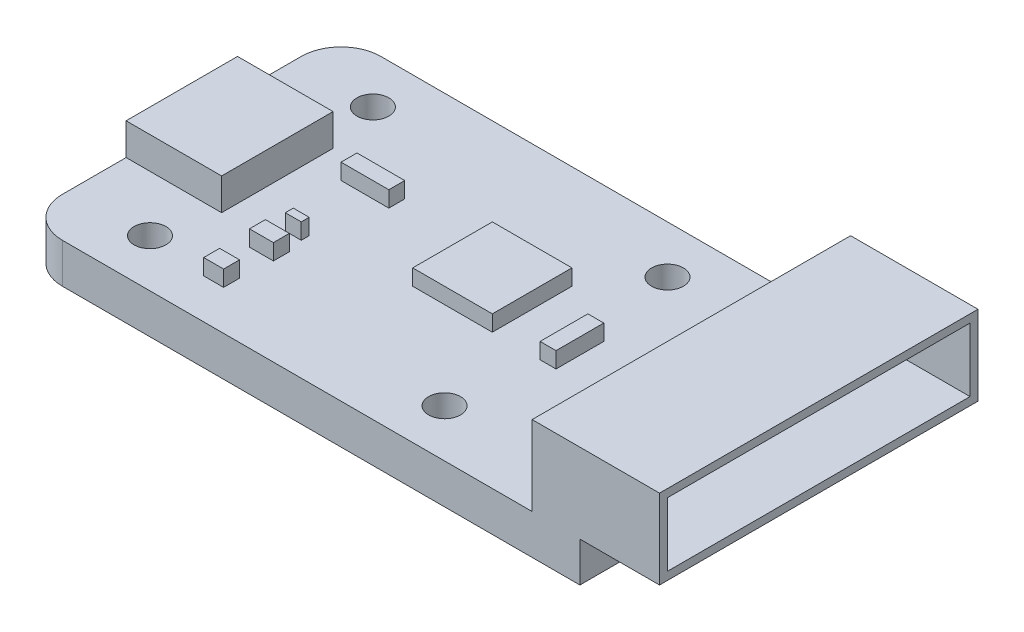
SolidWorks part; units mm, degrees
ref_plane "Front Plane" through (0, 0, 0) normal (0, 0, 1) x (1, 0, 0)
ref_plane "Top Plane" through (0, 0, 0) normal (0, 1, 0) x (1, 0, 0)
ref_plane "Right Plane" through (0, 0, 0) normal (1, 0, 0) x (0, 0, -1)
sketch "Sketch1" plane through (0, 0, 0) normal (0, 1, 0) x (1, 0, 0)
  line L1 (-17.5, -10) -> (17.5, -10)
  line L2 (-17.5, -10) -> (-17.5, 10)
  line L3 (-17.5, 10) -> (17.5, 10)
  line L4 (17.5, -10) -> (17.5, 10)
  line L5 (-17.5, -10) -> (17.5, 10) construction
  line L6 (-17.5, 10) -> (17.5, -10) construction
  point P0 (0, 0)
  dimension "D1" = 35
  dimension "D2" = 20
extrude "Boss-Extrude1" add sketch "Sketch1" along normal blind 2.5
fillet "Fillet1" radius 2.5 2 edges at (-17.5, 1.25, -10) (-17.5, 1.25, 10)
sketch "Sketch2" plane through (0, 2.5, 0) normal (0, 1, 0) x (1, 0, 0)
  line L0 (-17.5, 0) -> (17.5, 0) construction
  line L1 (-17.5, 7.5) -> (-17.5, -7.5) construction
  line L2 (17.5, -10) -> (17.5, 10) construction
  line L3 (17.5, 10) -> (-15, 10) construction
  circle A0 centre (-12.5, 7) radius 1
  circle A1 centre (6, 7) radius 1
  circle A2 centre (6, -7) radius 1
  circle A3 centre (-12.5, -7) radius 1
  point P12 (0, 0)
  dimension "D1" = 2
  dimension "D2" = 3
  dimension "D3" = 5
  dimension "D4" = 18.5
extrude "Cut-Extrude1" cut sketch "Sketch2" against normal up to surface (2.5 mm away) up to face at (-5.1726, 0, 0)
sketch "Sketch3" plane through (0, 2.5, 0) normal (0, 1, 0) x (1, 0, 0)
  line L0 (-17.5, 7.5) -> (-17.5, -7.5) construction
  line L1 (-11.5, -3.5) -> (-17.5, -3.5)
  line L2 (-11.5, -3.5) -> (-11.5, 3.5)
  line L3 (-11.5, 3.5) -> (-17.5, 3.5)
  line L4 (-17.5, -3.5) -> (-17.5, 3.5)
  line L5 (-11.5, -3.5) -> (-17.5, 3.5) construction
  line L6 (-11.5, 3.5) -> (-17.5, -3.5) construction
  point P0 (-14.5, 0)
  point P5 (0, 0)
  dimension "D1" = 7
  dimension "D2" = 6
  dimension "D3" = 3
extrude "Boss-Extrude2" add sketch "Sketch3" along normal blind 2
sketch "Sketch4" plane through (-17.5, 0, 0) normal (-1, 0, 0) x (0, 0, 1)
  line L1 (-3.25, 4.25) -> (3.25, 4.25)
  line L2 (-3.25, 4.25) -> (-3.25, 2.75)
  line L3 (-3.25, 2.75) -> (3.25, 2.75)
  line L4 (3.25, 4.25) -> (3.25, 2.75)
  line L5 (-3.25, 4.25) -> (3.25, 2.75) construction
  line L6 (-3.25, 2.75) -> (3.25, 4.25) construction
  point P0 (0, 3.5)
  point P5 (0, 0)
  point P7 (0, 0)
  dimension "D1" = 6.5
  dimension "D2" = 1.5
  dimension "D3" = 3.5
extrude "Cut-Extrude2" cut sketch "Sketch4" against normal blind 5.5
sketch "Sketch5" plane through (0, 2.5, 0) normal (0, 1, 0) x (1, 0, 0)
  line L0 (17.5, -10) -> (17.5, 10) construction
  line L1 (14.5, -10) -> (22.5, -10)
  line L2 (14.5, -10) -> (14.5, 10)
  line L3 (14.5, 10) -> (22.5, 10)
  line L4 (22.5, -10) -> (22.5, 10)
  line L5 (14.5, -10) -> (22.5, 10) construction
  line L6 (14.5, 10) -> (22.5, -10) construction
  point P0 (18.5, 0)
  point P7 (0, 0)
  dimension "D1" = 8
  dimension "D2" = 5
  dimension "D3" = 20
extrude "Boss-Extrude3" add sketch "Sketch5" along normal blind 5
sketch "Sketch6" plane through (22.5, 0, 0) normal (1, 0, 0) x (0, 0, -1)
  line L1 (-9.5, 3) -> (9.5, 3)
  line L2 (-9.5, 3) -> (-9.5, 7)
  line L3 (-9.5, 7) -> (9.5, 7)
  line L4 (9.5, 3) -> (9.5, 7)
  line L5 (-9.5, 3) -> (9.5, 7) construction
  line L6 (-9.5, 7) -> (9.5, 3) construction
  point P0 (0, 5)
  point P5 (0, 0)
  dimension "D1" = 5
  dimension "D2" = 4
  dimension "D3" = 19
extrude "Cut-Extrude3" cut sketch "Sketch6" against normal blind 7
sketch "Sketch7" plane through (0, 2.5, 0) normal (0, 1, 0) x (1, 0, 0)
  line L0 (-17.5, 7.5) -> (-17.5, 3.5) construction
  line L1 (-1.5, -1.5) -> (3.5, -1.5)
  line L2 (-1.5, -1.5) -> (-1.5, 3.5)
  line L3 (-1.5, 3.5) -> (3.5, 3.5)
  line L4 (3.5, -1.5) -> (3.5, 3.5)
  line L5 (-1.5, -1.5) -> (3.5, 3.5) construction
  line L6 (-1.5, 3.5) -> (3.5, -1.5) construction
  line L7 (14.5, 10) -> (-15, 10) construction
  point P0 (1, 1)
  dimension "D1" = 5
  dimension "D2" = 5
  dimension "D3" = 18.5
  dimension "D4" = 9
extrude "Boss-Extrude4" add sketch "Sketch7" along normal blind 1
sketch "Sketch8" plane through (0, 2.5, 0) normal (0, 1, 0) x (1, 0, 0)
  line L0 (-15, -10) -> (14.5, -10) construction
  line L1 (-8.625, -7.5) -> (-7.375, -7.5)
  line L2 (-8.625, -7.5) -> (-8.625, -6.5)
  line L3 (-8.625, -6.5) -> (-7.375, -6.5)
  line L4 (-7.375, -7.5) -> (-7.375, -6.5)
  line L5 (-8.625, -7.5) -> (-7.375, -6.5) construction
  line L6 (-8.625, -6.5) -> (-7.375, -7.5) construction
  line L7 (-8.75, -4.5) -> (-7.25, -4.5)
  line L8 (-8.75, -4.5) -> (-8.75, -3.5)
  line L9 (-8.75, -3.5) -> (-7.25, -3.5)
  line L10 (-7.25, -4.5) -> (-7.25, -3.5)
  line L11 (-8.75, -4.5) -> (-7.25, -3.5) construction
  line L12 (-8.75, -3.5) -> (-7.25, -4.5) construction
  line L13 (-8.5, -2.5) -> (-7.5, -2.5)
  line L14 (-8.5, -2.5) -> (-8.5, -2)
  line L15 (-8.5, -2) -> (-7.5, -2)
  line L16 (-7.5, -2.5) -> (-7.5, -2)
  line L17 (-8.5, -2.5) -> (-7.5, -2) construction
  line L18 (-8.5, -2) -> (-7.5, -2.5) construction
  line L19 (-9.5, 2) -> (-6.5, 2)
  line L20 (-9.5, 2) -> (-9.5, 3)
  line L21 (-9.5, 3) -> (-6.5, 3)
  line L22 (-6.5, 2) -> (-6.5, 3)
  line L23 (-9.5, 2) -> (-6.5, 3) construction
  line L24 (-9.5, 3) -> (-6.5, 2) construction
  line L25 (6.5, -1.5) -> (7.5, -1.5)
  line L26 (6.5, -1.5) -> (6.5, 1.5)
  line L27 (6.5, 1.5) -> (7.5, 1.5)
  line L28 (7.5, -1.5) -> (7.5, 1.5)
  line L29 (6.5, -1.5) -> (7.5, 1.5) construction
  line L30 (6.5, 1.5) -> (7.5, -1.5) construction
  line L31 (-17.5, -3.5) -> (-17.5, -7.5) construction
  line L33 (3.5, -1.5) -> (3.5, 3.5) construction
  line L35 (3.5, 3.5) -> (-1.5, 3.5) construction
  point P0 (-8, -7)
  point P5 (-8, -4)
  point P10 (-8, -2.25)
  point P15 (-8, 2.5)
  point P20 (7, 0)
  point P25 (0, 0)
  point P32 (7, 1.5)
  dimension "D1" = 1
  dimension "D2" = 3
  dimension "D3" = 3
  dimension "D4" = 1
  dimension "D5" = 1.25
  dimension "D6" = 1
  dimension "D7" = 1.5
  dimension "D8" = 1
  dimension "D9" = 1
  dimension "D10" = 0.5
  dimension "D11" = 3
  dimension "D12" = 2
  dimension "D13" = 1
  dimension "D14" = 4
  dimension "D15" = 9.5
  dimension "D16" = 3
  dimension "D17" = 2
extrude "Boss-Extrude5" add sketch "Sketch8" along normal blind 1
